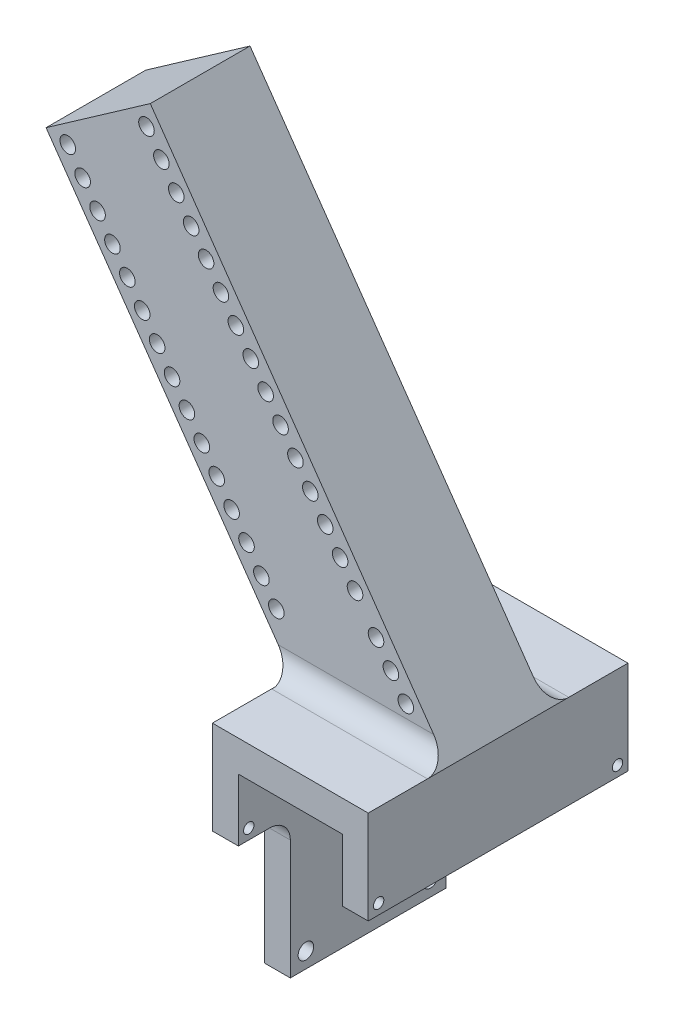
SolidWorks part; units mm, degrees
ref_plane "Front Plane" through (0, 0, 0) normal (0, 0, 1) x (1, 0, 0)
ref_plane "Top Plane" through (0, 0, 0) normal (0, 1, 0) x (1, 0, 0)
ref_plane "Right Plane" through (0, 0, 0) normal (1, 0, 0) x (0, 0, -1)
sketch "Sketch1" plane through (0, 0, 0) normal (0, 0, 1) x (1, 0, 0)
  line L0 (0, 0) -> (0, 18)
  line L2 (0, 18) -> (30, 18)
  line L3 (30, 18) -> (30, 0)
  line L4 (0, 0) -> (5, 0)
  line L5 (5, 0) -> (5, 12)
  line L6 (5, 12) -> (25, 12)
  line L7 (25, 12) -> (25, 0)
  line L8 (25, 0) -> (30, 0)
  dimension "D1" = 30
  dimension "D2" = 18
  dimension "D3" = 5
  dimension "D4" = 5
  dimension "D5" = 12
extrude "Boss-Extrude1" add sketch "Sketch1" along normal blind 50
sketch "Sketch2" plane through (0, 0, 0) normal (-1, 0, 0) x (0, 0, 1)
  line L0 (25, 0) -> (25, -41.6462) construction
  line L1 (50, 0) -> (0, 0) construction
  line L2 (40, 0) -> (10, 0)
  line L3 (10, 0) -> (10, -27)
  line L4 (10, -27) -> (40, -27)
  line L5 (40, 0) -> (40, -27)
  circle A0 centre (13, -24) radius 1.5
  circle A1 centre (37, -24) radius 1.5
  point P9 (0, 0)
  point P13 (25, -27)
  dimension "D3" = 3
  dimension "D1" = 15
  dimension "D2" = 27
  dimension "D4" = 3
  dimension "D5" = 3
extrude "Boss-Extrude2" add sketch "Sketch2" against normal blind 5
sketch "Sketch3" plane through (30, 0, 0) normal (1, 0, 0) x (0, 0, -1)
  line L0 (-50, 0) -> (0, 0) construction
  line L2 (-50, 0) -> (-50, 18) construction
  line L3 (-25, 0) -> (-25, 18) construction
  line L4 (-50, 18) -> (0, 18) construction
  circle A0 centre (-48, 2) radius 1
  circle A1 centre (-2, 2) radius 1
  dimension "D1" = 2
  dimension "D2" = 2
  dimension "D3" = 2
extrude "Cut-Extrude1" cut sketch "Sketch3" against normal through all both and the other way through all
sketch "Sketch4" plane through (0, 12, 0) normal (0, 1, 0) x (1, 0, 0)
  line L0 (30, -24.7105) -> (0, -24.7105) construction
  line L1 (30, -50) -> (30, 0) construction
  line L3 (25, -35.421) -> (25, -14)
  line L4 (30, 0) -> (0, 0) construction
  line L5 (25, -14) -> (5, -14)
  line L6 (5, -14) -> (5, -35.421)
  line L7 (25, -35.421) -> (5, -35.421)
  line L8 (5, -50) -> (5, 0) construction
  line L10 (25, -50) -> (25, 0) construction
  dimension "D1" = 14
ref_plane "Plane1" through (9, 9, 0) normal (0.7071, 0.7071, 0) x (0.7071, -0.7071, 0)
ref_plane "Plane2" through (24, 24, 0) normal (0.7071, 0.7071, 0) x (0.7071, -0.7071, 0)
ref_plane "Plane3" through (28.5875, 20.0172, 0) normal (0.8192, 0.5736, 0) x (0, 0, -1)
ref_plane "Plane4" through (8.1087, 5.6778, 0) normal (0.8192, 0.5736, 0) x (0, 0, -1)
sketch "Sketch5" plane through (28.5875, 20.0172, 0) normal (0.8192, 0.5736, 0) x (0, 0, -1)
  line L0 (-15.4, -2.4626) -> (-34.6, -2.4626)
  line L1 (-34.6, -2.4626) -> (-34.6, 97.5374)
  line L2 (-34.6, 97.5374) -> (-15.4, 97.5374)
  line L3 (-15.4, 97.5374) -> (-15.4, -2.4626)
  line L6 (-50, -2.4626) -> (-50, 14.7447) construction
  line L10 (-50, -2.4626) -> (0, -2.4626) construction
  dimension "D1" = 100
  dimension "D2" = 19.2
  dimension "D3" = 15.4
extrude "Boss-Extrude5" add sketch "Sketch5" against normal mid plane 49
extrude "Cut-Extrude3" cut sketch "Sketch5<2>" along normal blind 80
sketch "Sketch5<2>" plane through (28.5875, 20.0172, 0) normal (0.8192, 0.5736, 0) x (0, 0, -1) same geometry as "Sketch5"
extrude "Cut-Extrude4" cut sketch "Sketch4" against normal blind 80
sketch "Sketch9" plane through (0, 0, 34.6) normal (0, 0, 1) x (1, 0, 0)
  line L0 (-37.3923, 92.8889) -> (15.0455, 18) construction
  line L1 (-47.4269, 85.8626) -> (-27.3576, 99.9152) construction
  line L2 (30, 18) -> (0.091, 18) construction
  line L3 (-47.4269, 85.8626) -> (0.091, 18) construction
  circle A0 centre (-43.2487, 85.1259) radius 1.5
  circle A1 centre (-40.3808, 81.0301) radius 1.5
  circle A2 centre (-37.5129, 76.9343) radius 1.5
  circle A3 centre (-34.645, 72.8386) radius 1.5
  circle A4 centre (-31.7772, 68.7428) radius 1.5
  circle A5 centre (-28.9093, 64.6471) radius 1.5
  circle A6 centre (-26.0414, 60.5513) radius 1.5
  circle A7 centre (-23.1735, 56.4555) radius 1.5
  circle A8 centre (-20.3056, 52.3598) radius 1.5
  circle A9 centre (-17.4377, 48.264) radius 1.5
  circle A10 centre (-14.5699, 44.1683) radius 1.5
  circle A11 centre (-11.702, 40.0725) radius 1.5
  circle A12 centre (-8.8341, 35.9767) radius 1.5
  circle A13 centre (-5.9662, 31.881) radius 1.5
  circle A14 centre (-3.0983, 27.7852) radius 1.5
  circle A24 centre (21.8338, 24.4323) radius 1.5
  circle A25 centre (18.9659, 28.528) radius 1.5
  circle A26 centre (16.098, 32.6238) radius 1.5
  circle A27 centre (12.056, 38.3964) radius 1.5
  circle A28 centre (9.1881, 42.4921) radius 1.5
  circle A29 centre (6.3202, 46.5879) radius 1.5
  circle A30 centre (3.4523, 50.6837) radius 1.5
  circle A31 centre (0.5845, 54.7794) radius 1.5
  circle A32 centre (-2.2834, 58.8752) radius 1.5
  circle A33 centre (-5.1513, 62.9709) radius 1.5
  circle A34 centre (-8.0192, 67.0667) radius 1.5
  circle A35 centre (-10.8871, 71.1625) radius 1.5
  circle A36 centre (-13.755, 75.2582) radius 1.5
  circle A37 centre (-16.6228, 79.354) radius 1.5
  circle A38 centre (-19.4907, 83.4497) radius 1.5
  circle A39 centre (-22.3586, 87.5455) radius 1.5
  circle A40 centre (-25.2265, 91.6413) radius 1.5
  circle A41 centre (-28.0944, 95.737) radius 1.5
  circle A42 centre (11.2411, 7.3064) radius 1.5 [skipped]
  circle A43 centre (8.3732, 11.4022) radius 1.5 [skipped]
  circle A44 centre (5.5053, 15.4979) radius 1.5 [skipped]
  circle A45 centre (2.6374, 19.5937) radius 1.5 [skipped]
  circle A46 centre (-0.2305, 23.6895) radius 1.5 [skipped]
  dimension "D1" = 3
  dimension "D2" = 3
  dimension "D3" = 3
  dimension "D4" = 20
extrude "Cut-Extrude6" cut sketch "Sketch9" against normal up to surface (19.2 mm away) up to face at (-11.1734, 55.4444, 15.4)
fillet "Fillet3" radius 4 2 edges at (15.0455, 18, 15.4) (15.0455, 18, 34.6)
fillet "Fillet6" radius 4 2 edges at (2.5, 0, 40) (2.5, 0, 10)
